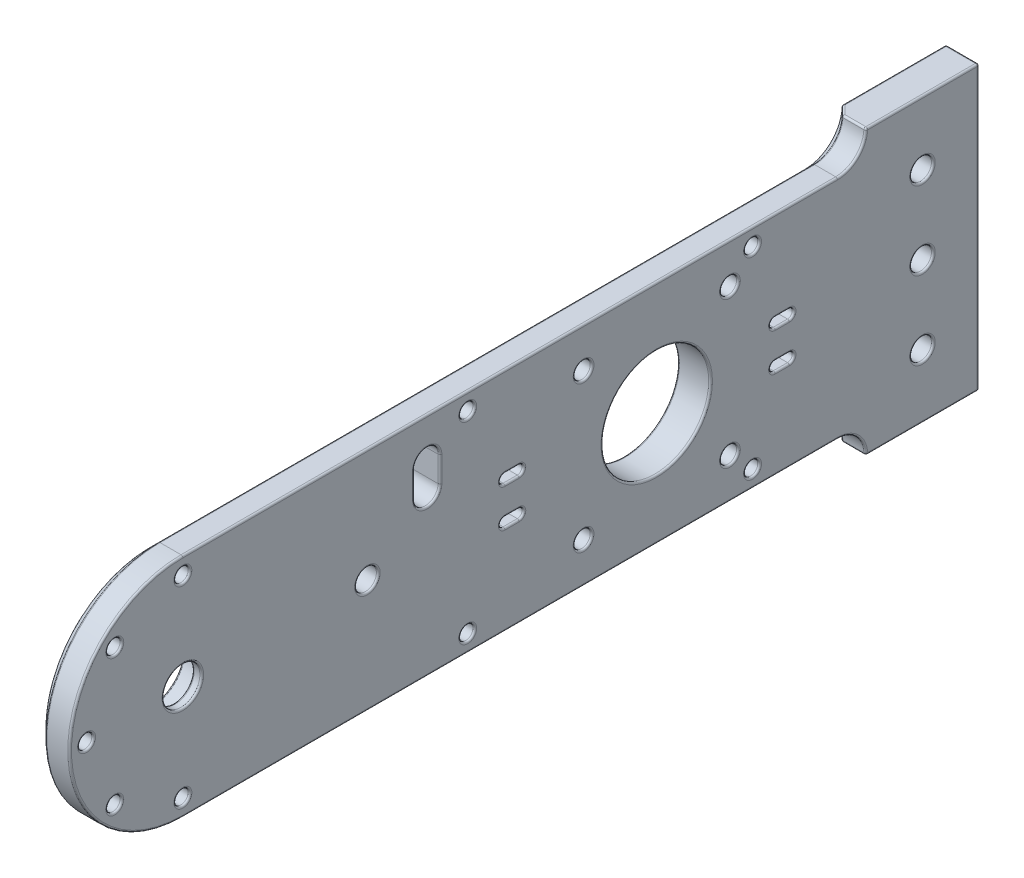
SolidWorks part; units mm, degrees
ref_plane "Front Plane" through (0, 0, 0) normal (0, 0, 1) x (1, 0, 0)
ref_plane "Top Plane" through (0, 0, 0) normal (0, 1, 0) x (1, 0, 0)
ref_plane "Right Plane" through (0, 0, 0) normal (1, 0, 0) x (0, 0, -1)
sketch "Sketch1" plane through (0, 0, 0) normal (1, 0, 0) x (0, 0, -1)
  line L0 (-12, 30) -> (-12, 16.5) construction
  line L1 (-168.7, 24) -> (-30, 24)
  line L2 (-83.8, -15.5) -> (-52.8, -15.5) construction
  line L3 (-83.8, -15.5) -> (-83.8, 15.5) construction
  line L4 (-83.8, 15.5) -> (-52.8, 15.5) construction
  line L5 (-52.8, -15.5) -> (-52.8, 15.5) construction
  line L6 (-83.8, -15.5) -> (-52.8, 15.5) construction
  line L7 (-83.8, 15.5) -> (-52.8, -15.5) construction
  line L8 (0, 24) -> (0, 0)
  line L9 (0, 0) -> (0, -24)
  line L11 (-12, 16.5) -> (-12, 0) construction
  line L12 (-12, 0) -> (-12, -16.5) construction
  line L13 (-12, -16.5) -> (-12, -30) construction
  line L14 (0, 24) -> (0, 30)
  line L15 (0, 30) -> (-12, 30)
  line L16 (-12, 30) -> (-24, 30)
  line L17 (-168.7, 0) -> (-68.3, 0) construction
  line L18 (-68.3, 0) -> (-12, 0) construction
  line L19 (-12, 0) -> (0, 0) construction
  line L20 (-12, 24) -> (0, 24)
  line L21 (0, -24) -> (0, -30)
  line L22 (0, -30) -> (-12, -30)
  line L23 (-12, -30) -> (-24, -30)
  line L24 (-30, -24) -> (-168.7, -24)
  circle A0 centre (-68.3, 0) radius 11.4
  arc A1 (-168.7, 24) -> (-168.7, -24) centre (-168.7, 0) ccw
  circle A2 centre (-83.8, 15.5) radius 1.8
  circle A3 centre (-52.8, 15.5) radius 1.8
  circle A4 centre (-83.8, -15.5) radius 1.8
  circle A5 centre (-52.8, -15.5) radius 1.8
  circle A6 centre (-12, 16.5) radius 2.3
  circle A7 centre (-12, 0) radius 2.3
  circle A8 centre (-12, -16.5) radius 2.3
  arc A9 (-30, 24) -> (-24, 30) centre (-30, 30) ccw
  arc A10 (-24, -30) -> (-30, -24) centre (-30, -30) ccw
  circle A11 centre (-168.7, 0) radius 4
  point P3 (-68.3, 0)
  dimension "D2" = 31
  dimension "D3" = 22.8
  dimension "D5" = 48
  dimension "D6" = 3.6
  dimension "D7" = 60
  dimension "D9" = 4.6
  dimension "D12" = 48
  dimension "D13" = 8
  dimension "D1" = 168.7
  dimension "D4" = 100.4
  dimension "D8" = 13.5
  dimension "D10" = 16.5
  dimension "D11" = 12
extrude "Boss-Extrude1" add sketch "Sketch1" along normal blind 7
ref_plane "Plane1" through (0, 0, 168.7) normal (0, 0, 1) x (1, 0, 0)
chamfer "Chamfer2" distance 2 angle 45 5 edges at (0, -25.7574, 25.7574) (0, -24, 99.35) (0, 0, 192.7) (0, 25.7574, 25.7574) (0, 24, 99.35)
ref_plane "Plane2" through (2.2, 0, 0) normal (-1, 0, 0) x (0, 0, 1)
sketch "Sketch3" plane through (7, 0, 0) normal (1, 0, 0) x (0, 0, -1)
  line L0 (-166.3575, 18.6988) -> (-67.5088, 6.3156) construction
  line L1 (-166.3575, -18.6988) -> (-67.5088, -6.3156) construction
  line L2 (-116.9332, 15.2072) -> (-116.9332, 9.8072) construction
  line L3 (-114.2332, 15.2072) -> (-114.2332, 9.8072)
  line L4 (-119.6332, 15.2072) -> (-119.6332, 9.8072)
  circle A0 centre (-168.7, 0) radius 18.845 construction
  circle A1 centre (-68.3, 0) radius 6.365 construction
  arc A2 (-114.2332, 15.2072) -> (-119.6332, 15.2072) centre (-116.9332, 15.2072) ccw
  arc A3 (-119.6332, 9.8072) -> (-114.2332, 9.8072) centre (-116.9332, 9.8072) ccw
  point P12 (-116.9332, 12.5072)
  point P22 (-116.9332, 12.5072)
  dimension "D1" = 37.69
  dimension "D2" = 12.73
  dimension "D3" = 2.7
  dimension "D4" = 5.4
  dimension "D5" = 2.7
extrude "Cut-Extrude2" cut sketch "Sketch3" against normal through all
sketch "Sketch4" plane through (0, 0, 0) normal (-1, 0, 0) x (0, 0, 1)
  line L0 (168.7, 0) -> (48, 0) construction
  line L1 (108.35, 0) -> (108.35, -20.4) construction
  line L2 (168.7, -3.919) -> (168.7, 3.919) construction
  circle A0 centre (108.35, -20.4) radius 1.5
  circle A1 centre (168.7, -20.4) radius 1.5
  circle A5 centre (168.7, 20.4) radius 1.5
  circle A6 centre (183.125, 14.425) radius 1.5
  circle A7 centre (189.1, 0) radius 1.5
  circle A8 centre (183.125, -14.425) radius 1.5
  circle A9 centre (154.275, 14.425) radius 1.5 [skipped]
  circle A10 centre (148.3, 0) radius 1.5 [skipped]
  circle A11 centre (154.275, -14.425) radius 1.5 [skipped]
  circle A12 centre (108.35, 20.4) radius 1.5
  circle A13 centre (48, -20.4) radius 1.5
  circle A14 centre (48, 20.4) radius 1.5
  point P23 (168.7, 0)
  dimension "D3" = 3
  dimension "D4" = 8
  dimension "D1" = 120.7
  dimension "D2" = 20.4
extrude "Cut-Extrude3" cut sketch "Sketch4" against normal through all
sketch "Sketch6" plane through (0, 0, 0) normal (-1, 0, 0) x (0, 0, 1)
  circle A0 centre (168.7, 0) radius 7.1
  dimension "D1" = 14.2
extrude "Cut-Extrude4" cut sketch "Sketch6" against normal blind 5
sketch "Sketch7" plane through (7, 0, 0) normal (1, 0, 0) x (0, 0, -1)
  line L0 (-168.7, 0) -> (-156, 0) construction
  line L1 (-168.7, 3.85) -> (-168.7, -3.85) construction
  line L2 (-156, 0) -> (-129.6, 0) construction
  circle A0 centre (-129.6, 0) radius 2.3
  dimension "D3" = 4.6
  dimension "D1" = 26.4
  dimension "D2" = 12.7
extrude "Cut-Extrude5" cut sketch "Sketch7" against normal blind 10
sketch "Sketch8" plane through (7, 0, 0) normal (1, 0, 0) x (0, 0, -1)
  line L0 (-68.3, 0) -> (-129.6, 0) construction
  line L1 (-98.95, 0) -> (-98.95, -4) construction
  line L2 (-97.45, -4) -> (-100.45, -4) construction
  line L3 (-97.45, -5) -> (-100.45, -5)
  line L4 (-97.45, -3) -> (-100.45, -3)
  line L5 (-97.45, 4) -> (-100.45, 4) construction
  line L6 (-97.45, 5) -> (-100.45, 5)
  line L7 (-97.45, 3) -> (-100.45, 3)
  line L8 (-68.3, 0) -> (-41.7, 0) construction
  line L9 (-168.7, 3.85) -> (-168.7, -3.85) construction
  line L10 (-41.7, 0) -> (-41.7, -4) construction
  line L11 (-40.2, -4) -> (-43.2, -4) construction
  line L12 (-40.2, -5) -> (-43.2, -5)
  line L13 (-40.2, -3) -> (-43.2, -3)
  line L14 (-40.2, 4) -> (-43.2, 4) construction
  line L15 (-40.2, 5) -> (-43.2, 5)
  line L16 (-40.2, 3) -> (-43.2, 3)
  circle A0 centre (-68.3, 0) radius 11.4 construction
  arc A1 (-97.45, -5) -> (-97.45, -3) centre (-97.45, -4) ccw
  arc A2 (-100.45, -3) -> (-100.45, -5) centre (-100.45, -4) ccw
  arc A3 (-97.45, 5) -> (-97.45, 3) centre (-97.45, 4) cw
  arc A4 (-100.45, 3) -> (-100.45, 5) centre (-100.45, 4) cw
  arc A5 (-40.2, -5) -> (-40.2, -3) centre (-40.2, -4) ccw
  arc A6 (-43.2, -3) -> (-43.2, -5) centre (-43.2, -4) ccw
  arc A7 (-40.2, 5) -> (-40.2, 3) centre (-40.2, 4) cw
  arc A8 (-43.2, 3) -> (-43.2, 5) centre (-43.2, 4) cw
  point P9 (-98.95, -4)
  point P16 (-98.95, 4)
  point P28 (-41.7, -4)
  point P35 (-41.7, 4)
  dimension "D1" = 4
  dimension "D3" = 1
  dimension "D2" = 3
  dimension "D4" = 127
extrude "Cut-Extrude6" cut sketch "Sketch8" against normal blind 10
fillet "Fillet1" radius 0.4 107 edges at (0, 12.5072, 114.2332) (0, 7.1072, 116.9332) (0, 12.5072, 119.6332) (7, 12.5072, 114.2332) (7, 7.1072, 116.9332) (7, 12.5072, 119.6332) (2, -25.7574, 25.7574) (2, -24, 99.35) (2, 0, 192.7) (2, 24, 99.35) (7, 25.7574, 25.7574) (7, 24, 99.35) (7, -25.7574, 25.7574) (7, -24, 99.35) (0, -24.3431, 24.3431) (0, -22, 99.35) (0, 24.3431, 24.3431) (0, 22, 99.35) (0, 14.425, 184.625) (7, 14.425, 184.625) (7, 0, 0) (0, 0, 0) (3.5, 30, 0) (7, 30, 12) (4.5, 30, 24) (1, 30, 23) (0, 30, 11) (7, -30, 12) (3.5, -30, 0) (0, -30, 11) (1, -30, 23) (4.5, -30, 24) (0, 16.5, 9.7) (7, 16.5, 9.7) (0, 0, 9.7) (7, 0, 9.7) (0, -16.5, 9.7) (7, -16.5, 9.7) (0, -15.5, 51) (7, -15.5, 51) (0, -20.4, 49.5) (7, -20.4, 49.5) (0, 0, 56.9) (7, 0, 56.9) (0, 15.5, 51) (7, 15.5, 51) (0, 20.4, 49.5) (7, 20.4, 49.5) (0, 15.5, 82) (7, 15.5, 82) (0, -15.5, 82) (7, -15.5, 82) (0, -20.4, 109.85) (7, -20.4, 109.85) (0, 20.4, 109.85) (7, 20.4, 109.85) (0, 17.9072, 116.9332) (7, 17.9072, 116.9332) (0, 0, 175.8) (5, 0, 175.8) (5, 0, 172.7) (7, 0, 164.7) (0, 20.4, 170.2) (7, 20.4, 170.2) (0, -20.4, 170.2) (7, -20.4, 170.2) (0, 0, 190.6) (7, 0, 190.6) (0, -14.425, 184.625) (7, -14.425, 184.625) (2, 25.7574, 25.7574) (7, 0, 192.7) (0, 0, 190.7) (0, 0, 127.3) (7, 0, 127.3) (0, -4, 96.45) (0, -5, 98.95) (0, -4, 101.45) (7, -4, 96.45) (7, -5, 98.95) (7, -4, 101.45) (0, 4, 96.45) (0, 3, 98.95) (0, 4, 101.45) (7, 4, 96.45) (7, 3, 98.95) (7, 4, 101.45) (0, -3, 98.95) (7, -3, 98.95) (0, 5, 98.95) (7, 5, 98.95) (0, -4, 39.2) (0, -5, 41.7) (0, -4, 44.2) (7, -4, 39.2) (7, -5, 41.7) (7, -4, 44.2) (0, 4, 39.2) (0, 3, 41.7) (0, 4, 44.2) (7, 4, 39.2) (7, 3, 41.7) (7, 4, 44.2) (0, -3, 41.7) (7, -3, 41.7) (0, 5, 41.7) (7, 5, 41.7)
